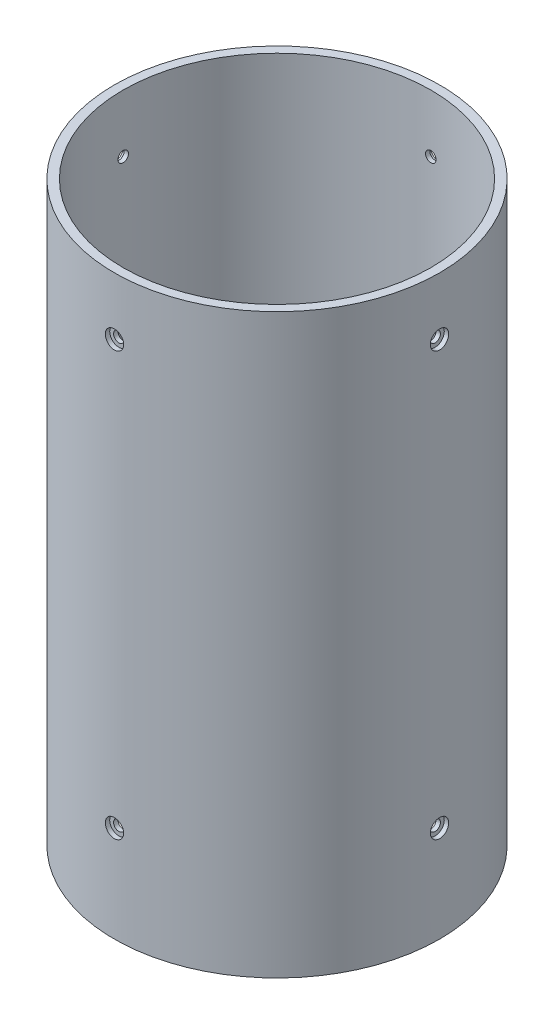
SolidWorks part; units mm, degrees
material "Hexcel AS4C (3000 Filaments)"
ref_plane "Front Plane" through (0, 0, 0) normal (0, 0, 1) x (1, 0, 0)
ref_plane "Top Plane" through (0, 0, 0) normal (0, 1, 0) x (1, 0, 0)
ref_plane "Right Plane" through (0, 0, 0) normal (1, 0, 0) x (0, 0, -1)
sketch "Sketch1" plane through (0, 0, 0) normal (0, 1, 0) x (1, 0, 0)
  circle A0 centre (0, 0) radius 50.8
  dimension "D1" = 101.6
extrude "Body Extrusion" add sketch "Sketch1" along normal blind 190.5 thin thin type one direction wall 2.921
ref_plane "Plane1" through (0, 0, 53.721) normal (0, 0, 1) x (1, 0, 0)
sketch "Sketch2" plane through (0, 0, 53.721) normal (0, 0, 1) x (1, 0, 0)
  line L0 (0, 190.5) -> (0, 0) construction
  line L1 (53.721, 190.5) -> (-53.721, 190.5) construction
  line L3 (50.8, 190.5) -> (-50.8, 190.5) construction
  circle A0 centre (0, 171.45) radius 1.7526
  dimension "D1" = 3.5052
  dimension "D2" = 19.05
extrude "Upper Bulkhead Holes" cut sketch "Sketch2" against normal up to next
pattern_circular "Upper Bulkhead Hole Pattern" count 4 over 360 about axis through (0, 190.5, 0) along (0, -1, 0) of "Upper Bulkhead Holes"
sketch "Sketch3" plane through (0, 0, 53.721) normal (0, 0, 1) x (1, 0, 0)
  line L0 (0, 190.5) -> (0, 0) construction
  line L1 (53.721, 190.5) -> (-53.721, 190.5) construction
  line L2 (50.8, 190.5) -> (-50.8, 190.5) construction
  circle A0 centre (0, 31.75) radius 1.7526
  dimension "D1" = 3.5052
  dimension "D2" = 31.75
  dimension "D3" = 158.75
extrude "Cut-Extrude1" cut sketch "Sketch3" against normal up to next
pattern_circular "CirPattern1" count 4 over 360 about axis through (0, 190.5, 0) along (0, -1, 0) of "Cut-Extrude1" reverse direction yes
sketch "Sketch4" plane through (0, 0, 53.721) normal (0, 0, 1) x (1, 0, 0)
  line L0 (0, 190.5) -> (0, 0) construction
  line L1 (50.8, 190.5) -> (-50.8, 190.5) construction
  line L2 (-50.8, 0) -> (50.8, 0) construction
  circle A0 centre (0, 171.45) radius 3.0226
  circle A1 centre (0, 31.75) radius 3.0226
  circle A2 centre (0, 31.75) radius 1.7526 construction
  circle A3 centre (0, 171.45) radius 1.7526 construction
  dimension "D1" = 1.27
  dimension "D2" = 1.27
extrude "Countersink" cut sketch "Sketch4" against normal blind 1.524
pattern_circular "CirPattern2" count 4 over 360 about axis through (0, 190.5, 0) along (0, -1, 0) of "Countersink"
equation "\"D2@Sketch4\"=\"D1@Sketch4\""
